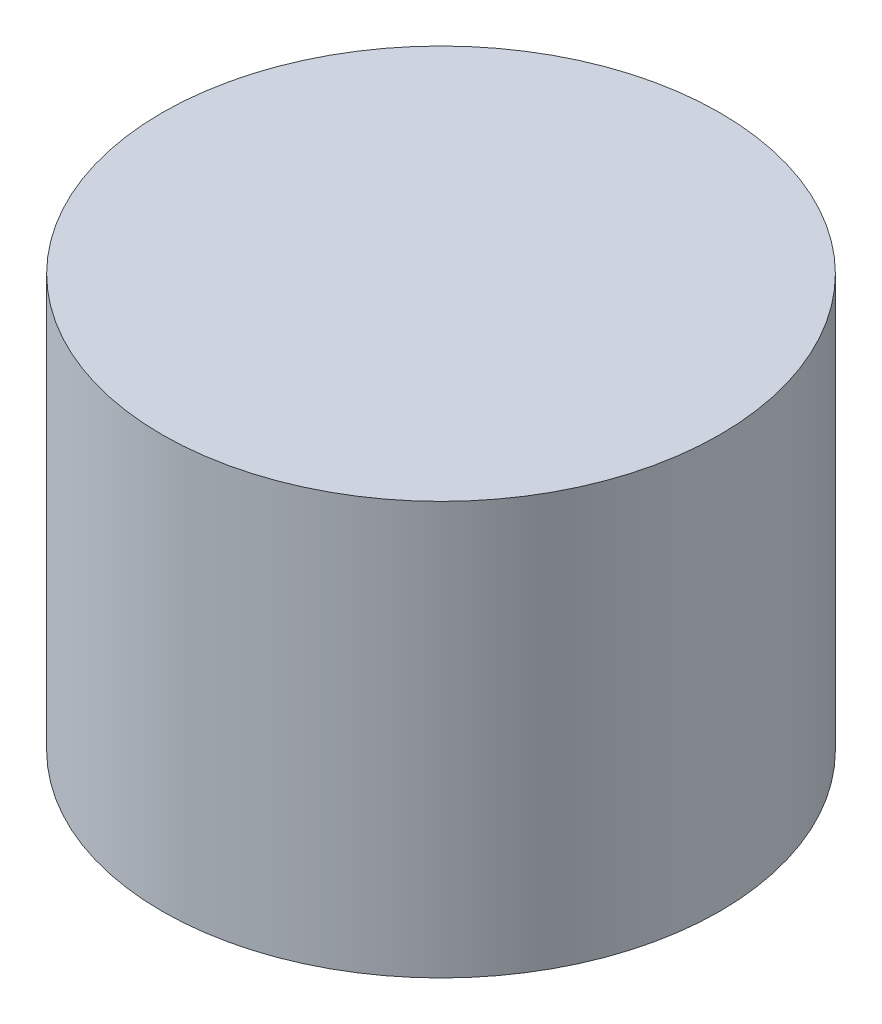
SolidWorks part; units mm, degrees
ref_plane "Plan de face" through (0, 0, 0) normal (0, 0, 1) x (1, 0, 0)
ref_plane "Plan de dessus" through (0, 0, 0) normal (0, 1, 0) x (1, 0, 0)
ref_plane "Plan de droite" through (0, 0, 0) normal (1, 0, 0) x (0, 0, -1)
sketch "Esquisse1" plane through (0, 0, 0) normal (0, 0, 1) x (1, 0, 0)
  line L0 (0, 0) -> (0, 4.0912) construction
  line L1 (-7.3944, 1.2544) -> (-11, -20)
  line L3 (-11, -20) -> (-25, -20) construction
  line L4 (-25, -20) -> (-25, 15)
  line L8 (0, 7.5) -> (0, 15)
  line L9 (0, 15) -> (-25, 15)
  line L11 (-11, -20) -> (-8, -20)
  line L12 (-8, -20) -> (-8, -22)
  line L13 (-8, -22) -> (-25, -22)
  line L14 (-25, -22) -> (-25, -20)
  arc A0 (-7.3944, 1.2544) -> (7.3944, 1.2544) centre (0, 0) cw construction
  arc A1 (-7.3944, 1.2544) -> (0, 7.5) centre (0, 0) cw
  point P5 (0, 0)
  point P16 (-11, -20.3195)
  dimension "D1" = 7.5
  dimension "D2" = 15
  dimension "D3" = 25
  dimension "D4" = 20
  dimension "D5" = 11
  dimension "D6" = 2
  dimension "D7" = 8
revolve "Révolution2" add sketch "Esquisse1" angle 360 about L8
sketch "Esquisse2" plane through (0, -22, 0) normal (0, -1, 0) x (1, 0, 0)
  line L1 (9.815, 0) -> (4.9075, 8.5)
  line L2 (4.9075, 8.5) -> (-4.9075, 8.5)
  line L3 (-4.9075, 8.5) -> (-9.815, 0)
  line L4 (-9.815, 0) -> (-4.9075, -8.5)
  line L5 (-4.9075, -8.5) -> (4.9075, -8.5)
  line L6 (4.9075, -8.5) -> (9.815, 0)
  circle A0 centre (0, 0) radius 8.5 construction
  dimension "D1" = 17
extrude "Enlèv. mat.-Extru.1" cut sketch "Esquisse2" against normal blind 4
fillet "Congé1" radius 2 1 edges at (11, -20, 0)
sketch "Esquisse3" plane through (0, -22, 0) normal (0, -1, 0) x (1, 0, 0)
  line L0 (0, 0) -> (10.6066, -10.6066) construction
  line L1 (0, 0) -> (0, -15) construction
  circle A0 centre (0, 0) radius 15 construction
  circle A1 centre (10.6066, -10.6066) radius 1.65
  circle A2 centre (-10.6066, -10.6066) radius 1.65
  circle A3 centre (-10.6066, 10.6066) radius 1.65
  circle A5 centre (10.6066, 10.6066) radius 1.65
  point P7 (13.686, 11.2419)
  point P13 (0, 0)
  point P14 (0, 0)
  dimension "D1" = 3.3
  dimension "D3" = 30
  dimension "D4" = 45
  dimension "D2" = 4
extrude "Enlèv. mat.-Extru.2" cut sketch "Esquisse3" against normal blind 20
